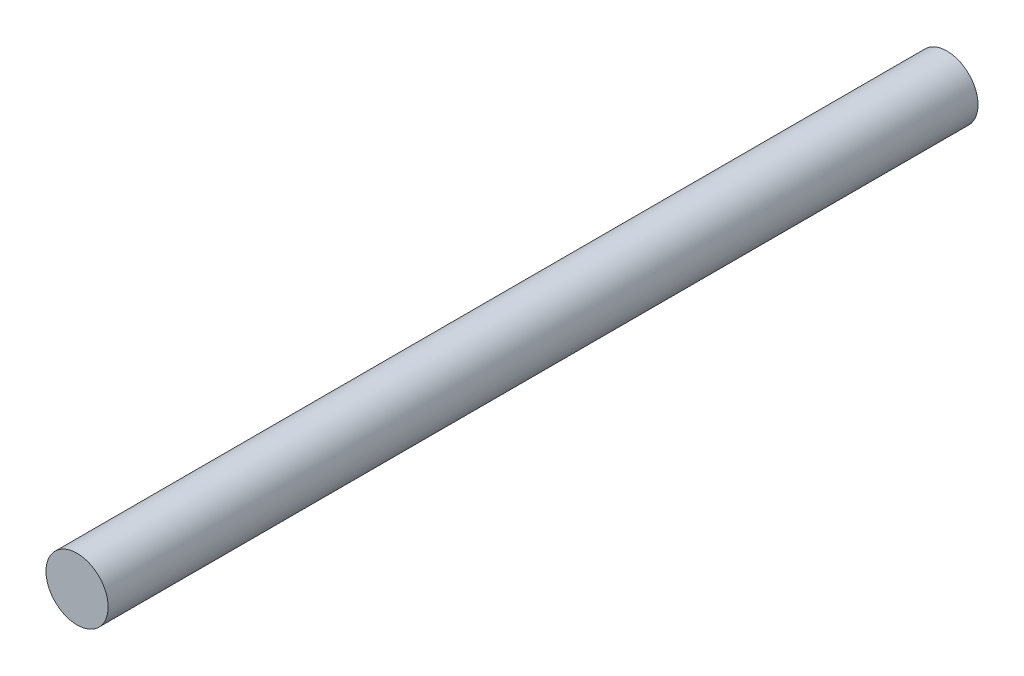
SolidWorks part; units mm, degrees
ref_plane "Front Plane" through (0, 0, 0) normal (0, 0, 1) x (1, 0, 0)
ref_plane "Top Plane" through (0, 0, 0) normal (0, 1, 0) x (1, 0, 0)
ref_plane "Right Plane" through (0, 0, 0) normal (1, 0, 0) x (0, 0, -1)
sketch "Sketch1" plane through (0, 0, 0) normal (0, 0, 1) x (1, 0, 0)
  circle A0 centre (0, 0) radius 5
  dimension "D1" = 10
extrude "Boss-Extrude1" add sketch "Sketch1" along normal blind 150
sketch "Sketch2" plane through (0, 0, 0) normal (0, 0, -1) x (-1, 0, 0)
  circle A1 centre (0, 0) radius 5
  circle A2 centre (0, 0) radius 5
  dimension "D1" = 0
extrude "Cut-Extrude1" cut sketch "Sketch2" against normal blind 10
